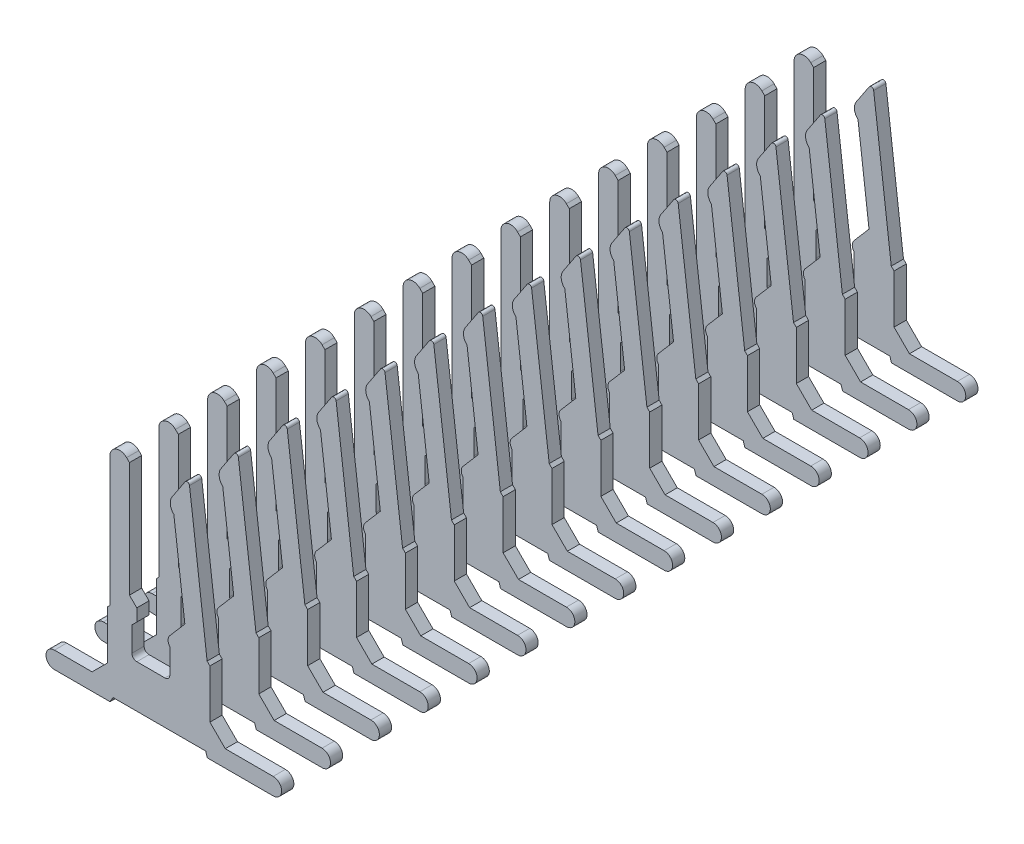
SolidWorks part; units mm, degrees
ref_plane "Płaszczyzna przednia" through (0, 0, 0) normal (0, 0, 1) x (1, 0, 0)
ref_plane "Płaszczyzna górna" through (0, 0, 0) normal (0, 1, 0) x (1, 0, 0)
ref_plane "Płaszczyzna prawa" through (0, 0, 0) normal (1, 0, 0) x (0, 0, -1)
sketch "Sketch1" plane through (0, 0, 0) normal (0, 0, 1) x (1, 0, 0)
  line L52 (1.1543, 1.456) -> (1.0969, 1.5134)
  line L53 (1.0969, 1.5134) -> (0.7371, 4.4438)
  line L54 (0.6458, 4.4654) -> (0.3804, 4.0662)
  line L55 (0.4165, 3.7723) -> (0.6414, 1.9409)
  line L56 (0.6414, 1.9409) -> (0.3345, 1.5836)
  line L57 (0.3345, 1.3881) -> (0.3345, 0.8832)
  line L58 (0.2345, 0.7832) -> (-0.3421, 0.7832)
  line L59 (-0.4421, 0.8832) -> (-0.4421, 1.3849)
  line L60 (-0.4421, 1.3849) -> (-0.3421, 1.4849)
  line L61 (-0.3421, 1.4849) -> (-0.3421, 1.7374)
  line L62 (-0.3421, 1.7374) -> (-0.4921, 1.8874)
  line L63 (-0.4921, 1.8874) -> (-0.4921, 4.2369)
  line L64 (-0.4921, 4.2369) -> (-0.5507, 4.2955)
  line L65 (-0.8921, 4.154) -> (-0.8921, 1.506)
  line L66 (-0.8921, 1.506) -> (-0.9421, 1.456)
  line L67 (-0.9421, 1.456) -> (-0.9421, 0.4604)
  line L68 (-0.9421, 0.4604) -> (-1.2566, 0.1459)
  line L69 (-1.2566, 0.1459) -> (-2.027, 0.1459)
  line L70 (-2.027, -0.2) -> (-0.8897, -0.2)
  line L71 (-0.8897, -0.2) -> (-0.8292, -0.0952)
  line L72 (-0.8292, -0.0952) -> (1.0681, -0.0952)
  line L73 (1.0681, -0.0952) -> (1.1019, -0.2)
  line L74 (1.1019, -0.2) -> (2.4489, -0.2)
  line L75 (2.4489, 0.1459) -> (1.4688, 0.1459)
  line L76 (1.4688, 0.1459) -> (1.1543, 0.4604)
  line L77 (1.1543, 0.4604) -> (1.1543, 1.456)
  arc A16 (0.7371, 4.4438) -> (0.6458, 4.4654) centre (0.6875, 4.4377) ccw
  arc A17 (0.3804, 4.0662) -> (0.4165, 3.7723) centre (0.5698, 3.9403) ccw
  arc A18 (0.3345, 1.5836) -> (0.3345, 1.3881) centre (0.4483, 1.4859) ccw
  arc A19 (0.2345, 0.7832) -> (0.3345, 0.8832) centre (0.2345, 0.8832) ccw
  arc A20 (-0.4421, 0.8832) -> (-0.3421, 0.7832) centre (-0.3421, 0.8832) ccw
  arc A21 (-0.5507, 4.2955) -> (-0.8921, 4.154) centre (-0.6921, 4.154) ccw
  arc A22 (-2.027, 0.1459) -> (-2.027, -0.2) centre (-2.027, -0.027) ccw
  arc A23 (2.4489, -0.2) -> (2.4489, 0.1459) centre (2.4489, -0.027) ccw
extrude "Boss-Extrude1" add sketch "Sketch1" along normal blind 0.25
pattern_linear "LPattern1" count 15 spacing 1 along (0, 0, -1) of bodies 101
